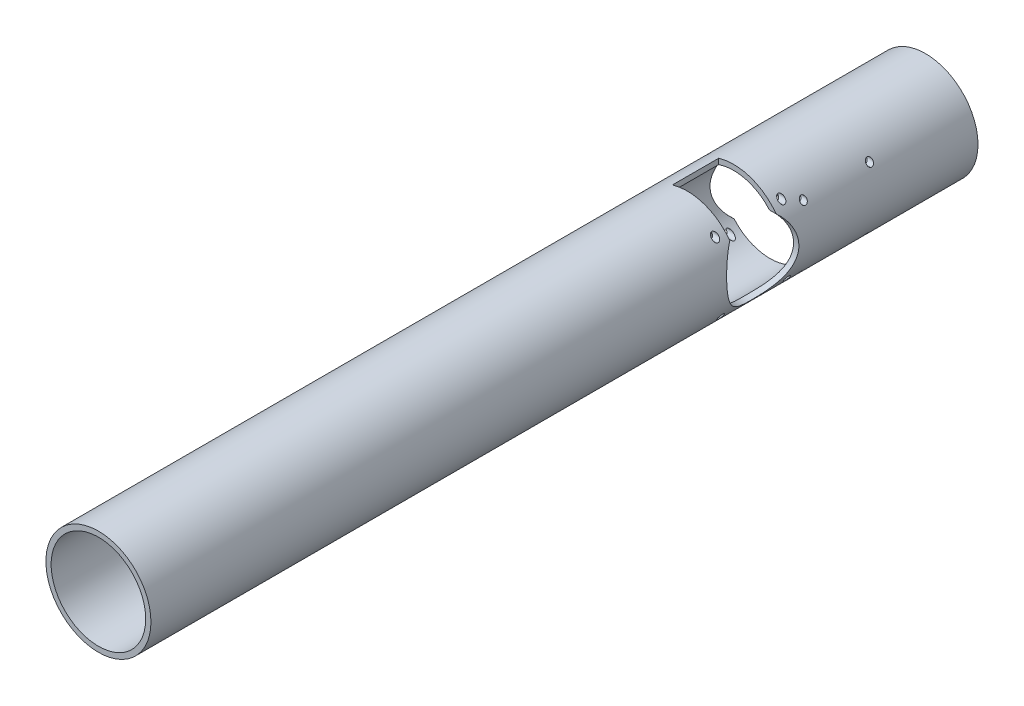
SolidWorks part; units mm, degrees
ref_plane "Front Plane" through (0, 0, 0) normal (0, 0, 1) x (1, 0, 0)
ref_plane "Top Plane" through (0, 0, 0) normal (0, 1, 0) x (1, 0, 0)
ref_plane "Right Plane" through (0, 0, 0) normal (1, 0, 0) x (0, 0, -1)
sketch "Sketch1" plane through (0, 0, 0) normal (0, 0, 1) x (1, 0, 0)
  circle A0 centre (0, 0) radius 31.75
  circle A1 centre (0, 0) radius 28.575
  dimension "D1" = 63.5
  dimension "D2" = 57.15
extrude "Boss-Extrude1" add sketch "Sketch1" along normal blind 250 and the other way blind 250 contours A1 | A0 region at (0, 0, 0)
sketch "Sketch2" plane through (0, 0, 0) normal (1, 0, 0) x (0, 0, -1)
  circle A2 centre (170, -2) radius 21.75
  dimension "D1" = 43.5
  dimension "D2" = 170
  dimension "D3" = 2
extrude "Cut-Extrude1" cut sketch "Sketch2" against normal through all
sketch "Sketch3" plane through (0, 0, 0) normal (1, 0, 0) x (0, 0, -1)
  circle A1 centre (120, 2) radius 21.75
  dimension "D1" = 120
  dimension "D2" = 43.5
  dimension "D3" = 2
extrude "Cut-Extrude2" cut sketch "Sketch3" along normal through all
sketch "Sketch5" plane through (0, 0, 0) normal (1, 0, 0) x (0, 0, -1)
  line L1 (184, -12.75) -> (156, -12.75)
  line L2 (184, -12.75) -> (184, -34.75)
  line L3 (184, -34.75) -> (156, -34.75)
  line L4 (156, -12.75) -> (156, -34.75)
  line L5 (184, -12.75) -> (156, -34.75) construction
  line L6 (184, -34.75) -> (156, -12.75) construction
  circle A0 centre (170, -2) radius 21.75 construction
  circle A1 centre (170, -2) radius 21.75 construction
  point P0 (170, -23.75)
  dimension "D1" = 28
  dimension "D2" = 22
  dimension "D3" = 170
extrude "Cut-Extrude4" cut sketch "Sketch5" against normal through all from offset 9
sketch "Sketch6" plane through (0, 0, 0) normal (1, 0, 0) x (0, 0, -1)
  line L1 (106, 34.75) -> (134, 34.75)
  line L2 (106, 34.75) -> (106, 12.75)
  line L3 (106, 12.75) -> (134, 12.75)
  line L4 (134, 34.75) -> (134, 12.75)
  line L5 (106, 34.75) -> (134, 12.75) construction
  line L6 (106, 12.75) -> (134, 34.75) construction
  circle A0 centre (120, 2) radius 21.75 construction
  circle A1 centre (120, 2) radius 21.75 construction
  point P0 (120, 23.75)
  dimension "D1" = 28
  dimension "D2" = 22
  dimension "D3" = 120
extrude "Cut-Extrude5" cut sketch "Sketch6" along normal through all from offset 9 offset against normal yes
sketch "Sketch8" plane through (0, 0, 0) normal (1, 0, 0) x (0, 0, -1)
  line L1 (80, 42) -> (160, 42)
  line L2 (80, 42) -> (80, -38)
  line L3 (80, -38) -> (160, -38)
  line L4 (160, 42) -> (160, -38)
  line L5 (80, 42) -> (160, -38) construction
  line L6 (80, -38) -> (160, 42) construction
  point P0 (120, 2)
  dimension "D1" = 80
  dimension "D2" = 80
sketch "Sketch9" plane through (0, 0, 0) normal (1, 0, 0) x (0, 0, -1)
  line L0 (80, 42) -> (160, -38) construction
  line L1 (80, -38) -> (160, 42) construction
  circle A0 centre (100, 22) radius 2
  circle A1 centre (140, 22) radius 2
  circle A2 centre (140, -18) radius 2
  circle A3 centre (100, -18) radius 2
  dimension "D2" = 4
  dimension "D4" = 4
  dimension "D6" = 4
  dimension "D8" = 4
  dimension "D1" = 20
  dimension "D3" = 20
  dimension "D5" = 20
  dimension "D7" = 20
extrude "Cut-Extrude7" cut sketch "Sketch9" against normal through all both and the other way through all
sketch "Sketch10" plane through (0, 0, 0) normal (1, 0, 0) x (0, 0, -1)
  line L1 (210, 38) -> (130, 38)
  line L2 (210, 38) -> (210, -42)
  line L3 (210, -42) -> (130, -42)
  line L4 (130, 38) -> (130, -42)
  line L5 (210, 38) -> (130, -42) construction
  line L6 (210, -42) -> (130, 38) construction
  point P0 (170, -2)
  dimension "D1" = 80
  dimension "D2" = 80
sketch "Sketch11" plane through (0, 0, 0) normal (1, 0, 0) x (0, 0, -1)
  line L0 (210, 38) -> (130, -42) construction
  line L1 (210, -42) -> (130, 38) construction
  circle A0 centre (190, 18) radius 2
  circle A1 centre (150, 18) radius 2
  circle A2 centre (150, -22) radius 2
  circle A3 centre (190, -22) radius 2
  dimension "D5" = 4
  dimension "D6" = 4
  dimension "D7" = 4
  dimension "D8" = 4
  dimension "D1" = 20
  dimension "D2" = 20
  dimension "D3" = 20
  dimension "D4" = 20
extrude "Cut-Extrude8" cut sketch "Sketch11" against normal through all both and the other way through all
